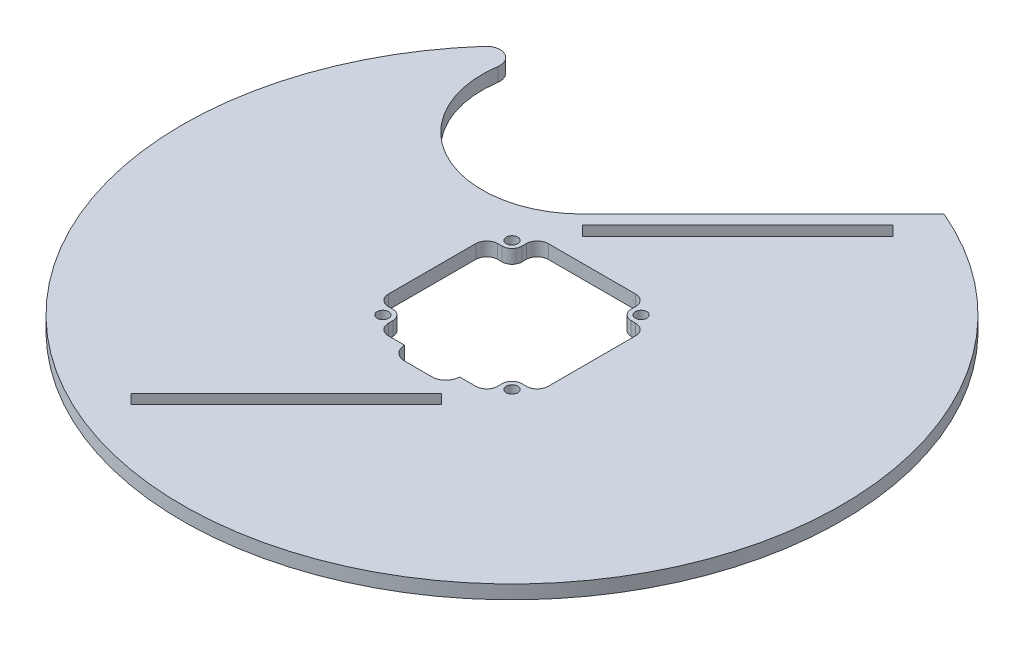
SolidWorks part; units mm, degrees
ref_plane "前基準面" through (0, 0, 0) normal (0, 0, 1) x (1, 0, 0)
ref_plane "上基準面" through (0, 0, 0) normal (0, 1, 0) x (1, 0, 0)
ref_plane "右基準面" through (0, 0, 0) normal (1, 0, 0) x (0, 0, -1)
sketch "草圖1" plane through (0, 0, 0) normal (0, 1, 0) x (1, 0, 0)
  line L2 (-119.8141, -6.677) -> (6.677, 119.8141) construction
  line L3 (-11.9239, 37.5736) -> (44.6447, 94.1421)
  line L4 (-28.5, 28.5) -> (28.5, 28.5) construction
  line L5 (-28.5, 28.5) -> (-28.5, -28.5) construction
  line L6 (-28.5, -28.5) -> (28.5, -28.5) construction
  line L7 (28.5, 28.5) -> (28.5, -28.5) construction
  line L8 (-11.9239, 37.5736) -> (-15.4594, 41.1091)
  line L9 (-18.8989, 23.5) -> (-18.8989, 25.1) construction
  line L10 (-25.1, 18.8989) -> (-23.5, 18.8989) construction
  line L11 (-18.8989, 23.5) -> (-18.8989, 25.1) construction
  line L12 (-25.1, 18.8989) -> (-23.5, 18.8989) construction
  line L13 (23.5, 18.8989) -> (25.1, 18.8989) construction
  line L14 (18.8989, 25.1) -> (18.8989, 23.5) construction
  line L15 (18.8989, -23.5) -> (18.8989, -25.1) construction
  line L16 (25.1, -18.8989) -> (23.5, -18.8989) construction
  line L17 (-23.5, -18.8989) -> (-25.1, -18.8989) construction
  line L18 (-18.8989, -25.1) -> (-18.8989, -23.5) construction
  line L19 (-15.8989, 28.1) -> (15.8989, 28.1) construction
  line L20 (28.1, 15.8989) -> (28.1, -15.8989) construction
  line L21 (-15.8989, -28.1) -> (15.8989, -28.1) construction
  line L22 (-28.1, 15.8989) -> (-28.1, -15.8989) construction
  line L23 (-19.8989, 23.5) -> (-19.8989, 25.1)
  line L24 (-15.8989, 29.1) -> (15.8989, 29.1)
  line L25 (19.8989, 25.1) -> (19.8989, 23.5)
  line L26 (23.5, 19.8989) -> (25.1, 19.8989)
  line L27 (29.1, 15.8989) -> (29.1, -15.8989)
  line L28 (25.1, -19.8989) -> (23.5, -19.8989)
  line L29 (19.8989, -23.5) -> (19.8989, -25.1)
  line L30 (-15.8989, -29.1) -> (15.8989, -29.1)
  line L31 (-19.8989, -25.1) -> (-19.8989, -23.5)
  line L32 (-23.5, -19.8989) -> (-25.1, -19.8989)
  line L33 (-29.1, 15.8989) -> (-29.1, -15.8989)
  line L34 (-25.1, 19.8989) -> (-23.5, 19.8989)
  line L35 (44.6447, 94.1421) -> (41.1091, 97.6777)
  line L36 (41.1091, 97.6777) -> (-15.4594, 41.1091)
  line L37 (41.1091, 97.6777) -> (51.7157, 108.2843) construction
  line L38 (-44.6447, -94.1421) -> (-41.1091, -97.6777)
  line L39 (-18.9949, 44.6447) -> (46.8409, 110.4805)
  line L40 (11.9239, -37.5736) -> (-44.6447, -94.1421)
  line L41 (-41.1091, -97.6777) -> (15.4594, -41.1091)
  line L42 (11.9239, -37.5736) -> (15.4594, -41.1091)
  arc A20 (-89.6013, 79.8224) -> (46.8409, 110.4805) centre (0, 0) ccw
  circle A24 centre (0, 0) radius 20
  arc A27 (-15.8989, 28.1) -> (-18.8989, 25.1) centre (-15.8989, 25.1) ccw construction
  arc A28 (-25.1, 18.8989) -> (-28.1, 15.8989) centre (-25.1, 15.8989) ccw construction
  arc A29 (-23.5, 18.8989) -> (-18.8989, 23.5) centre (-23.5, 23.5) ccw construction
  arc A30 (-15.8989, 28.1) -> (-18.8989, 25.1) centre (-15.8989, 25.1) ccw construction
  arc A31 (-25.1, 18.8989) -> (-28.1, 15.8989) centre (-25.1, 15.8989) ccw construction
  arc A32 (-23.5, 18.8989) -> (-18.8989, 23.5) centre (-23.5, 23.5) ccw construction
  arc A33 (28.1, 15.8989) -> (25.1, 18.8989) centre (25.1, 15.8989) ccw construction
  arc A34 (18.8989, 25.1) -> (15.8989, 28.1) centre (15.8989, 25.1) ccw construction
  arc A35 (18.8989, 23.5) -> (23.5, 18.8989) centre (23.5, 23.5) ccw construction
  arc A36 (15.8989, -28.1) -> (18.8989, -25.1) centre (15.8989, -25.1) ccw construction
  arc A37 (25.1, -18.8989) -> (28.1, -15.8989) centre (25.1, -15.8989) ccw construction
  arc A38 (23.5, -18.8989) -> (18.8989, -23.5) centre (23.5, -23.5) ccw construction
  arc A39 (-28.1, -15.8989) -> (-25.1, -18.8989) centre (-25.1, -15.8989) ccw construction
  arc A40 (-18.8989, -25.1) -> (-15.8989, -28.1) centre (-15.8989, -25.1) ccw construction
  arc A41 (-18.8989, -23.5) -> (-23.5, -18.8989) centre (-23.5, -23.5) ccw construction
  arc A42 (-23.5, 19.8989) -> (-19.8989, 23.5) centre (-23.5, 23.5) ccw
  arc A43 (-15.8989, 29.1) -> (-19.8989, 25.1) centre (-15.8989, 25.1) ccw
  arc A44 (19.8989, 25.1) -> (15.8989, 29.1) centre (15.8989, 25.1) ccw
  arc A45 (19.8989, 23.5) -> (23.5, 19.8989) centre (23.5, 23.5) ccw
  arc A46 (29.1, 15.8989) -> (25.1, 19.8989) centre (25.1, 15.8989) ccw
  arc A47 (25.1, -19.8989) -> (29.1, -15.8989) centre (25.1, -15.8989) ccw
  arc A48 (23.5, -19.8989) -> (19.8989, -23.5) centre (23.5, -23.5) ccw
  arc A49 (15.8989, -29.1) -> (19.8989, -25.1) centre (15.8989, -25.1) ccw
  arc A50 (-19.8989, -25.1) -> (-15.8989, -29.1) centre (-15.8989, -25.1) ccw
  arc A51 (-19.8989, -23.5) -> (-23.5, -19.8989) centre (-23.5, -23.5) ccw
  arc A52 (-29.1, -15.8989) -> (-25.1, -19.8989) centre (-25.1, -15.8989) ccw
  arc A53 (-25.1, 19.8989) -> (-29.1, 15.8989) centre (-25.1, 15.8989) ccw
  circle A54 centre (0, 0) radius 80 construction
  circle A55 centre (-79.7214, -6.6703) radius 35 construction
  circle A56 centre (84.2635, 190.3295) radius 35 construction
  arc A58 (-80.9211, 75.7688) -> (-18.9949, 44.6447) centre (-44.8066, 70.4563) ccw
  arc A59 (-89.6013, 79.8224) -> (-80.9211, 75.7688) centre (-85.8679, 76.4965) cw
  point P16 (0, 28.5)
  point P18 (-28.5, 0)
  dimension "D1" = 4
  dimension "D2" = 240
  dimension "D3" = 160
  dimension "D4" = 40
  dimension "D6" = 1
  dimension "D8" = 45
  dimension "D11" = 15
  dimension "D12" = 70
  dimension "D13" = 5
  dimension "D15" = 2
  dimension "D5" = 57
  dimension "D9" = 5
  dimension "D10" = 80
  dimension "D7" = 45
  dimension "D14" = 5
extrude "填料-伸長1" add sketch "草圖1" against normal blind 5 contours A20 A53 L34 A42 L23 A43 L24 A44 L25 A45 L26 A46 L27 A47 L28 A48 L29 A49 L30 A50 L31 A51 L32 A52 L33 region at (16.2758, 0, -75.2097)
sketch "草圖2" plane through (0, 0, 0) normal (0, 1, 0) x (1, 0, 0)
  line L1 (-23.5, 23.5) -> (23.5, 23.5)
  line L2 (-23.5, 23.5) -> (-23.5, -23.5)
  line L3 (-23.5, -23.5) -> (23.5, -23.5)
  line L4 (23.5, 23.5) -> (23.5, -23.5)
  point P9 (23.5, 0)
  point P15 (0, 23.5)
  dimension "D1" = 47
sketch "草圖5" plane through (0, 0, 0) normal (0, 1, 0) x (1, 0, 0)
  line L0 (-5, -29.1) -> (5, -29.1) construction
  line L1 (-15.8989, -29.1) -> (15.8989, -29.1) construction
  line L2 (-5, -24.1) -> (5, -24.1)
  line L3 (-5, -34.1) -> (5, -34.1)
  arc A0 (-5, -24.1) -> (-5, -34.1) centre (-5, -29.1) ccw
  arc A1 (5, -34.1) -> (5, -24.1) centre (5, -29.1) ccw
  point P4 (0, -29.1)
  point P9 (0, 0)
  point P11 (0, -29.1)
  dimension "D1" = 10
  dimension "D2" = 10
extrude "除料-伸長1" cut sketch "草圖5" against normal through all both and the other way through all contours L2 A1 L3 A0
hole_wizard "M5 螺紋孔1" positions "草圖3" profile "草圖4" tap size "M5" standard "ISO" end condition through all
sketch "草圖3" plane through (0, 0, 0) normal (0, 1, 0) x (1, 0, 0)
  point P13 (23.5, 23.5)
  point P16 (23.5, -23.5)
  point P19 (-23.5, -23.5)
  point P22 (-23.5, 23.5)
sketch "草圖4" plane through (23.5, 0, -23.5) normal (1, 0, 0) x (0, 0, 1)
  line L0 (0, 0) -> (0, 5)
  line L1 (0, 5) -> (2.1, 5)
  line L2 (2.1, 5) -> (2.1, 0)
  line L5 (2.1, 0) -> (0, 0)
  line L11 (0, -6.35) -> (0, 107.95) construction
  dimension "貫穿螺孔鑽直徑" = 4.2
  dimension "貫穿螺孔鑽深度" = 5
cosmetic thread "鑽孔螺紋1" parameters "D2"=5
cosmetic thread "鑽孔螺紋2" parameters "D2"=5
cosmetic thread "鑽孔螺紋3" parameters "D2"=5
cosmetic thread "鑽孔螺紋4" parameters "D2"=5
